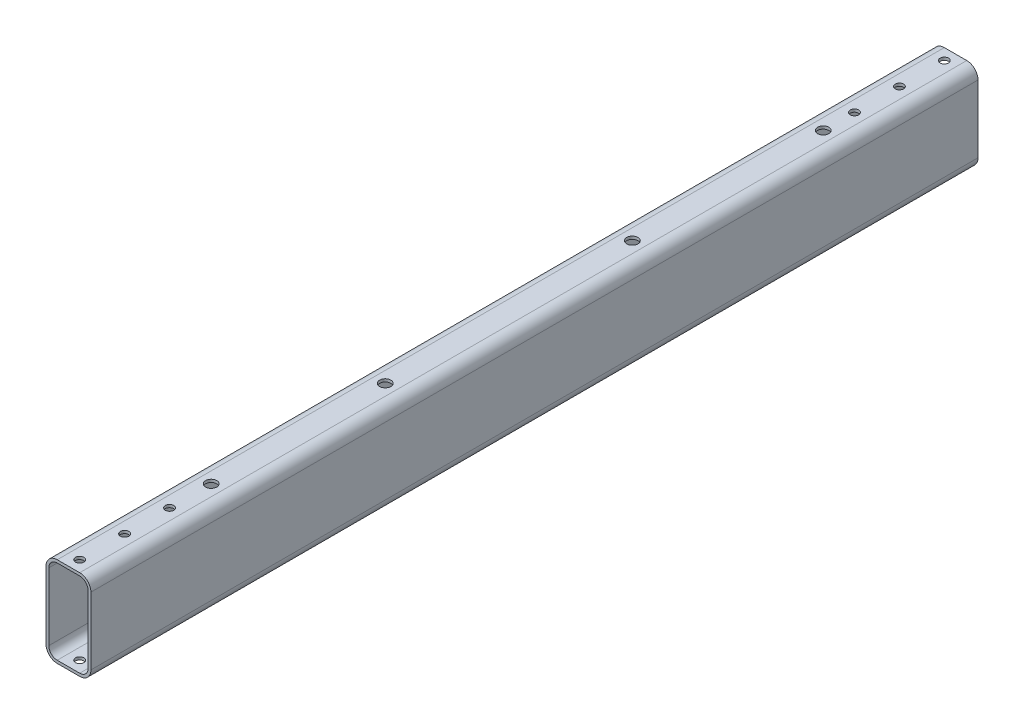
SolidWorks part; units mm, degrees
material "6061-T6 (SS)"
ref_plane "Front Plane" through (0, 0, 0) normal (0, 0, 1) x (1, 0, 0)
ref_plane "Top Plane" through (0, 0, 0) normal (0, 1, 0) x (1, 0, 0)
ref_plane "Right Plane" through (0, 0, 0) normal (1, 0, 0) x (0, 0, -1)
sketch "Sketch1" plane through (0, 0, 0) normal (0, 0, 1) x (1, 0, 0)
  line L1 (-6.35, -25.4) -> (6.35, -25.4)
  line L2 (-12.7, -19.05) -> (-12.7, 19.05)
  line L3 (-6.35, 25.4) -> (6.35, 25.4)
  line L4 (12.7, -19.05) -> (12.7, 19.05)
  line L5 (-12.7, -25.4) -> (12.7, 25.4) construction
  line L6 (-12.7, 25.4) -> (12.7, -25.4) construction
  arc A0 (-12.7, -19.05) -> (-6.35, -25.4) centre (-6.35, -19.05) ccw
  arc A1 (6.35, -25.4) -> (12.7, -19.05) centre (6.35, -19.05) ccw
  arc A2 (6.35, 25.4) -> (12.7, 19.05) centre (6.35, 19.05) cw
  arc A3 (-12.7, 19.05) -> (-6.35, 25.4) centre (-6.35, 19.05) cw
  point P0 (0, 0)
  dimension "D3" = 6.35
  dimension "D1" = 50.8
  dimension "D2" = 25.4
extrude "Extrude-Thin1" add sketch "Sketch1" along normal blind 501.65 thin thin type one direction reverse wall 1.5875
hole_wizard "3/16 (0.1875) Diameter Hole1" positions "3DSketch1" profile "Sketch3" hole size "3/16" standard "ANSI Inch" end condition through all
sketch3d "3DSketch1"
  line L1 (6.35, 25.4, 0) -> (-6.35, 25.4, 0) construction
  line L6 (0, 25.4, 501.65) -> (0, 25.4, 0) construction
  line L7 (6.35, 25.4, 501.65) -> (-6.35, 25.4, 501.65) construction
  point P57 (0, 25.4, 6.35)
  point P59 (0, 25.4, 31.75)
  point P61 (0, 25.4, 57.15)
  point P63 (0, 25.4, 469.9)
  point P65 (0, 25.4, 444.5)
  point P67 (0, 25.4, 495.3)
  dimension "D1" = 25.4
  dimension "D2" = 25.4
  dimension "D3" = 6.35
  dimension "D4" = 25.4
  dimension "D5" = 25.4
  dimension "D6" = 6.35
sketch "Sketch3" plane through (0, 25.4, 495.3) normal (1, 0, 0) x (0, 0, 1)
  line L0 (0, 0) -> (0, 50.8)
  line L1 (0, 50.8) -> (2.3812, 50.8)
  line L2 (2.3812, 50.8) -> (2.3812, 0)
  line L5 (2.3812, 0) -> (0, 0)
  line L11 (0, -6.35) -> (0, 107.95) construction
  dimension "Thru Hole Dia." = 4.7625
  dimension "Thru Hole Depth" = 50.8
hole_wizard "3/16 (0.195) Diameter Hole1" positions "Sketch4" profile "Sketch5" hole size "3/16" standard "ANSI Inch" end condition up to next
sketch "Sketch4" plane through (0, -25.4, 0) normal (0, -1, 0) x (-1, 0, 0)
  point P28 (3.175, -81.2609)
  point P31 (-3.175, -106.6609)
  point P34 (3.175, -132.0609)
  point P37 (-3.175, -157.4609)
  point P40 (3.175, -182.8609)
  point P43 (3.175, -335.2609)
  point P46 (-3.175, -360.6609)
  point P49 (3.175, -386.0609)
  point P52 (-3.175, -411.4609)
  point P60 (-3.175, -208.2609)
  point P63 (3.175, -233.6609)
  point P66 (-3.175, -259.0609)
  point P69 (3.175, -284.4609)
  point P72 (-3.175, -309.8609)
sketch "Sketch5" plane through (-3.175, -25.4, 81.2609) normal (1, 0, 0) x (0, 0, -1)
  line L0 (0, 0) -> (0, 1.5875)
  line L1 (0, 1.5875) -> (2.4765, 1.5875)
  line L2 (2.4765, 1.5875) -> (2.4765, 0)
  line L5 (2.4765, 0) -> (0, 0)
  line L11 (0, -6.35) -> (0, 107.95) construction
  dimension "Thru Hole Dia." = 4.953
  dimension "Thru Hole Depth" = 1.5875
hole_wizard "1/4 (0.25) Diameter Hole1" positions "Sketch7" profile "Sketch6" hole size "1/4" standard "ANSI Inch"
sketch "Sketch7" plane through (0, 25.4, 0) normal (0, 1, 0) x (1, 0, 0)
  point P6 (0, -74.8359)
  point P9 (0, -420.9388)
  point P23 (0, -322.504)
  point P26 (0, -182.7859)
sketch "Sketch6" plane through (0, 25.4, 74.8359) normal (1, 0, 0) x (0, 0, 1)
  line L0 (0, 0) -> (0, 27.3077)
  line L1 (0, 27.3077) -> (3.175, 25.4)
  line L2 (3.175, 25.4) -> (3.175, 0)
  line L5 (3.175, 0) -> (0, 0)
  line L10 (0, 27.3077) -> (-3.175, 25.4) construction
  line L11 (0, -6.35) -> (0, 107.95) construction
  dimension "Hole Dia." = 6.35
  dimension "Hole Depth" = 25.4
  dimension "Drill Angle" = 118
